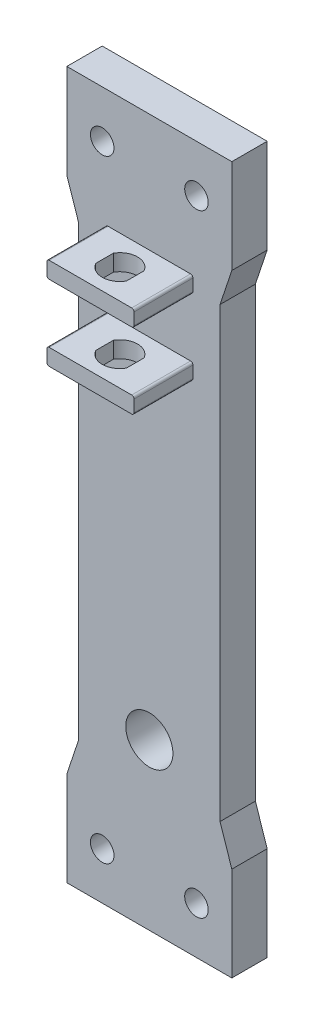
SolidWorks part; units mm, degrees
ref_plane "Front Plane" through (0, 0, 0) normal (0, 0, 1) x (1, 0, 0)
ref_plane "Top Plane" through (0, 0, 0) normal (0, 1, 0) x (1, 0, 0)
ref_plane "Right Plane" through (0, 0, 0) normal (1, 0, 0) x (0, 0, -1)
sketch "Sketch1" plane through (0, 0, 0) normal (0, 0, 1) x (1, 0, 0)
  line L0 (0, 150) -> (0, -150) construction
  line L1 (-35, 150) -> (35, 150)
  line L2 (35, 150) -> (35, 110)
  line L3 (35, 110) -> (30, 95)
  line L4 (30, 95) -> (30, -95)
  line L5 (30, -95) -> (35, -110)
  line L6 (35, -110) -> (35, -150)
  line L7 (35, -150) -> (-35, -150)
  line L8 (-177.3008, 0) -> (162.8823, 0) construction
  line L9 (-35, -110) -> (-35, -150)
  line L10 (-30, -95) -> (-35, -110)
  line L11 (-30, 95) -> (-30, -95)
  line L12 (-35, 110) -> (-30, 95)
  line L13 (-35, 150) -> (-35, 110)
  line L15 (-17.5, 100) -> (17.5, 100)
  line L16 (-18.5, 99) -> (-18.5, 94)
  line L17 (-17.5, 93) -> (17.5, 93)
  line L18 (18.5, 99) -> (18.5, 94)
  line L19 (-18.5, 100) -> (18.5, 93) construction
  line L20 (-18.5, 93) -> (18.5, 100) construction
  line L21 (-17.5, 68) -> (17.5, 68)
  line L22 (-18.5, 67) -> (-18.5, 62)
  line L23 (-17.5, 61) -> (17.5, 61)
  line L24 (18.5, 67) -> (18.5, 62)
  line L25 (-18.5, 68) -> (18.5, 61) construction
  line L26 (-18.5, 61) -> (18.5, 68) construction
  arc A0 (17.5, 100) -> (18.5, 99) centre (17.5, 99) cw
  arc A1 (17.5, 93) -> (18.5, 94) centre (17.5, 94) ccw
  arc A2 (-18.5, 94) -> (-17.5, 93) centre (-17.5, 94) ccw
  arc A3 (-17.5, 100) -> (-18.5, 99) centre (-17.5, 99) ccw
  arc A4 (17.5, 68) -> (18.5, 67) centre (17.5, 67) cw
  arc A5 (17.5, 61) -> (18.5, 62) centre (17.5, 62) ccw
  arc A6 (-18.5, 62) -> (-17.5, 61) centre (-17.5, 62) ccw
  arc A7 (-17.5, 68) -> (-18.5, 67) centre (-17.5, 67) ccw
  circle A8 centre (-20, 130) radius 5
  circle A9 centre (20, 130) radius 5
  circle A10 centre (0, -80) radius 10
  circle A11 centre (20, -130) radius 5
  circle A12 centre (-20, -130) radius 5
  point P17 (0, 96.5)
  point P34 (0, 64.5)
  dimension "D9" = 1
  dimension "D13" = 1
  dimension "D16" = 10
  dimension "D18" = 20
  dimension "D1" = 300
  dimension "D2" = 190
  dimension "D3" = 40
  dimension "D4" = 35
  dimension "D5" = 60
  dimension "D6" = 50
  dimension "D7" = 7
  dimension "D8" = 37
  dimension "D10" = 25
  dimension "D11" = 7
  dimension "D12" = 37
  dimension "D14" = 20
  dimension "D15" = 20
  dimension "D17" = 70
extrude "Boss-Extrude1" add sketch "Sketch1" against normal blind 15 contours L1 L2 L3 L4 L5 L6 L7 L9 L10 L11 L12 L13
extrude "Cut-Extrude1" cut sketch "Sketch1<3>" against normal blind 15 contours A8 | A9 | A10 | A11 | A12
sketch "Sketch1<3>" plane through (0, 0, 0) normal (0, 0, 1) x (1, 0, 0) same geometry as "Sketch1"
extrude "Boss-Extrude2" add sketch "Sketch1<4>" along normal blind 25 contours L17 A1 L18 A0 L15 A3 L16 A2 | L23 A5 L24 A4 L21 A7 L22 A6
sketch "Sketch1<4>" plane through (0, 0, 0) normal (0, 0, 1) x (1, 0, 0) same geometry as "Sketch1"
sketch "Sketch2" plane through (0, 100, 0) normal (0, 1, 0) x (1, 0, 0)
  line L0 (0, 19.5047) -> (0, -27.9354) construction
  line L2 (-17.5, -25) -> (17.5, -25) construction
  line L3 (-6.5, -8.7583) -> (-6.5, -16.2417)
  line L4 (6.5, -8.7583) -> (6.5, -16.2417)
  arc A1 (-6.5, -16.2417) -> (6.5, -16.2417) centre (0, -12.5) ccw
  arc A2 (6.5, -8.7583) -> (-6.5, -8.7583) centre (0, -12.5) ccw
  dimension "D1" = 12.5
  dimension "D2" = 15
  dimension "D3" = 6.5
extrude "Cut-Extrude3" cut sketch "Sketch2" against normal through all contours A1 L4 A2 L3
